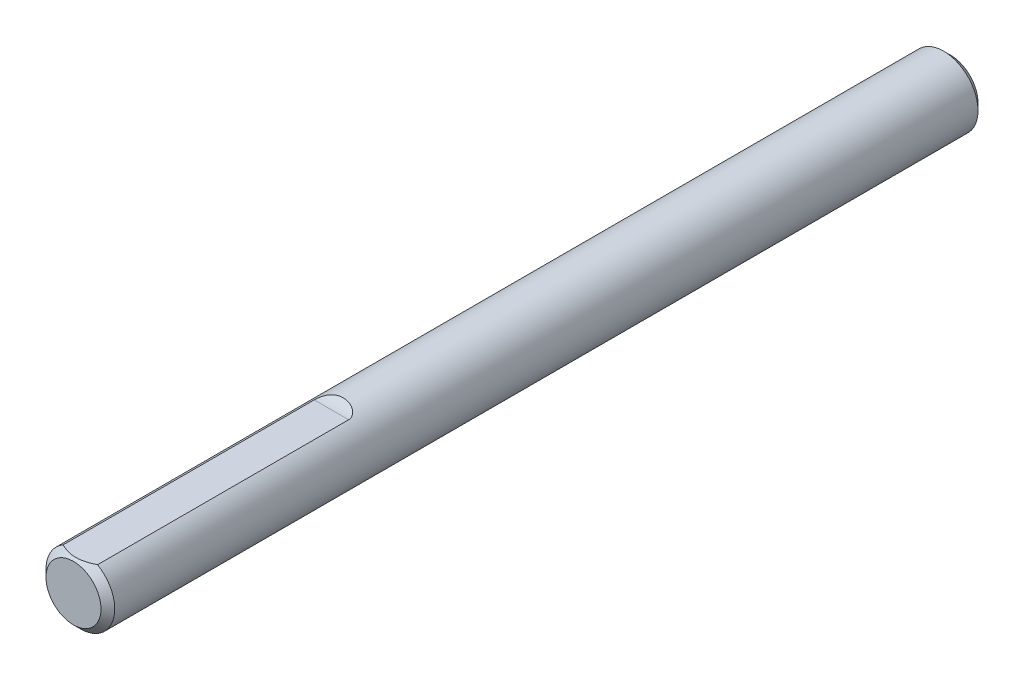
SolidWorks part; units mm, degrees
ref_plane "Front" through (0, 0, 0) normal (0, 0, 1) x (1, 0, 0)
ref_plane "Top" through (0, 0, 0) normal (0, 1, 0) x (1, 0, 0)
ref_plane "Right" through (0, 0, 0) normal (1, 0, 0) x (0, 0, -1)
sketch "Sketch1" plane through (0, 0, 0) normal (0, 0, 1) x (1, 0, 0)
  circle A0 centre (0, 0) radius 3.175
  dimension "D1" = 6.35
extrude "Extrude1" add sketch "Sketch1" along normal mid plane 80.9625
chamfer "Chamfer1" distance 0.635 angle 45 2 edges at (3.175, 0, -40.4812) (3.175, 0, 40.4812)
ref_plane "Plane1" through (0, 0, 15.0812) normal (0, 0, 1) x (1, 0, 0)
sketch "Sketch13" plane through (0, 0, 15.0812) normal (0, 0, 1) x (1, 0, 0)
  line L3 (-1.5875, 2.7496) -> (1.5875, 2.7496)
  circle A0 centre (0, 0) radius 3.175 construction
  arc A1 (1.5875, 2.7496) -> (-1.5875, 2.7496) centre (0, 0) ccw
  dimension "D1" = 3.175
extrude "Extrude7" cut sketch "Sketch13" along normal through all
fillet "Fillet1" radius 1.5875 1 edges at (0, 2.7496, 15.0812)
equation "\"D1@Chamfer1\" = \"D1@Sketch1\" * .1"
equation "\"D1@Sketch13\" = \"D1@Sketch1\" * .5"
